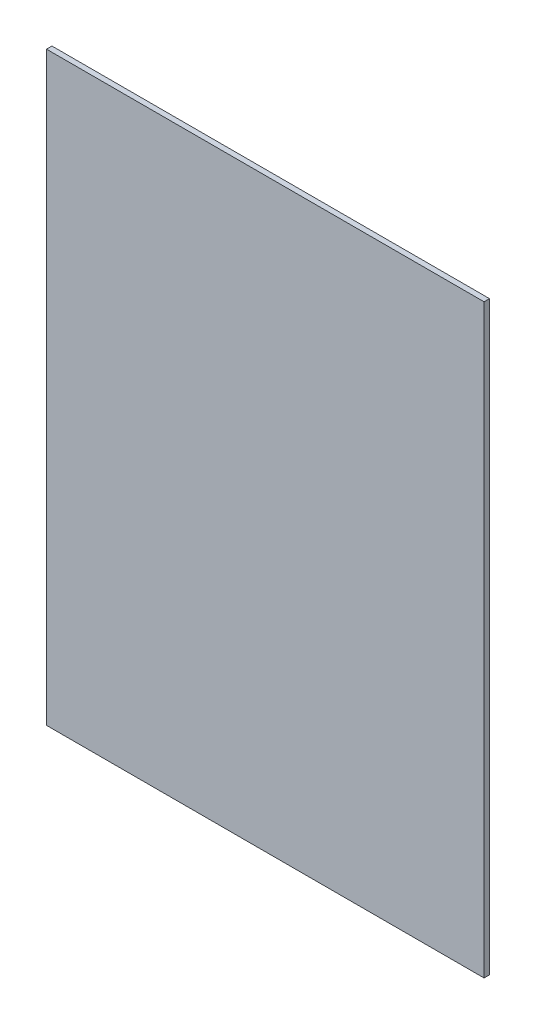
SolidWorks part; units mm, degrees
material "PE High Density Film"
ref_plane "Front Plane" through (0, 0, 0) normal (0, 0, 1) x (1, 0, 0)
ref_plane "Top Plane" through (0, 0, 0) normal (0, 1, 0) x (1, 0, 0)
ref_plane "Right Plane" through (0, 0, 0) normal (1, 0, 0) x (0, 0, -1)
sketch "Sketch1" plane through (0, 0, 0) normal (0, 0, 1) x (1, 0, 0)
  line L1 (0, 0) -> (510.54, 0)
  line L2 (0, 0) -> (0, 683.26)
  line L3 (0, 683.26) -> (510.54, 683.26)
  line L4 (510.54, 0) -> (510.54, 683.26)
  dimension "D1" = 683.26
  dimension "D2" = 510.54
extrude "Boss-Extrude1" add sketch "Sketch1" along normal blind 6.35
